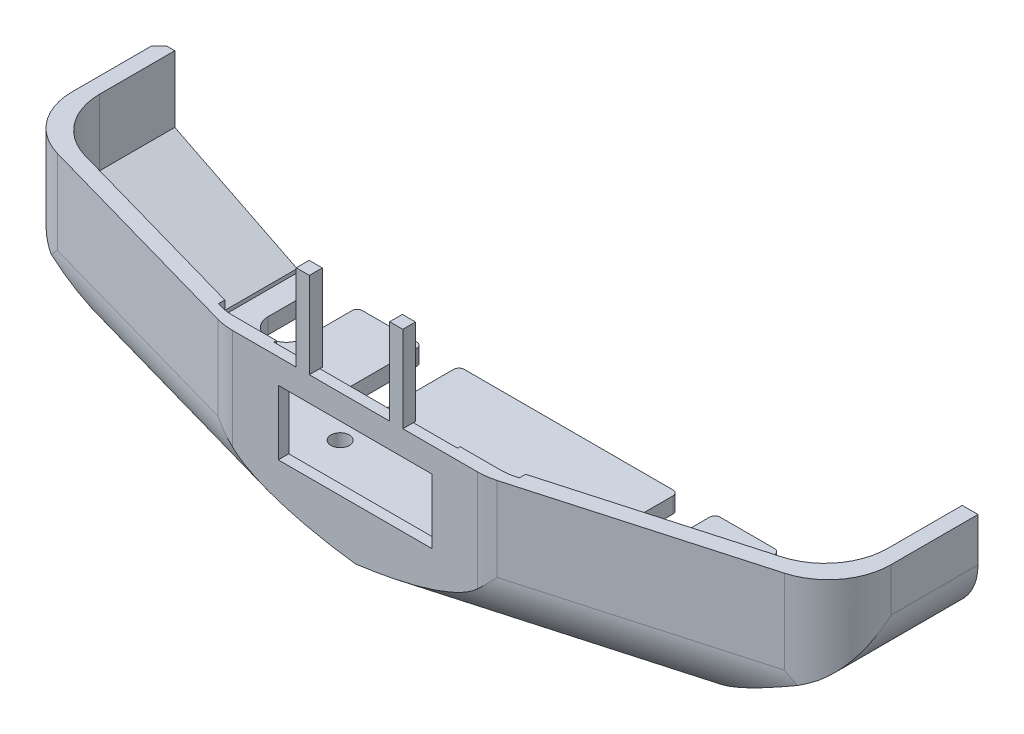
SolidWorks part; units mm, degrees
material "ABS"
ref_plane "Front Plane" through (0, 0, 0) normal (0, 0, 1) x (1, 0, 0)
ref_plane "Top Plane" through (0, 0, 0) normal (0, 1, 0) x (1, 0, 0)
ref_plane "Right Plane" through (0, 0, 0) normal (1, 0, 0) x (0, 0, -1)
sketch "Sketch1" plane through (0, 0, 0) normal (0, 0, 1) x (1, 0, 0)
  line L0 (-78, -21.6306) -> (78, -21.6306) construction
  line L1 (-51, -40.6306) -> (51, -40.6306)
  line L2 (-78, -27.1306) -> (-78, -12.6306)
  line L3 (-78, -12.6306) -> (78, -12.6306)
  line L4 (78, -27.1306) -> (78, -12.6306)
  line L8 (0, -21.6306) -> (0, 0) construction
  line L9 (78, -27.1306) -> (51, -40.6306)
  line L13 (-51, -40.6306) -> (-78, -27.1306)
  line L15 (0, -40.6306) -> (0, -21.6306) construction
  dimension "D1" = 9
  dimension "D2" = 156
  dimension "D3" = 13.5
  dimension "D5" = 102
  dimension "D6" = 19
extrude "Boss-Extrude1" add sketch "Sketch1" along normal blind 30 and the other way blind 10.64
sketch "Sketch2" plane through (0, -12.6306, 0) normal (0, 1, 0) x (1, 0, 0)
  line L0 (-78, -15) -> (-25, -30)
  line L1 (-78, -30) -> (-78, 10.64) construction
  line L2 (78, -30) -> (-78, -30) construction
  line L3 (-25, -30) -> (25, -30)
  line L4 (25, -30) -> (78, -15)
  line L5 (78, -30) -> (78, 10.64) construction
  line L6 (78, -15) -> (78, -44.6495)
  line L7 (78, -44.6495) -> (-78, -44.6495)
  line L8 (-78, -44.6495) -> (-78, -15)
  dimension "D1" = 50
  dimension "D2" = 15
extrude "Cut-Extrude1" cut sketch "Sketch2" against normal through all
shell "Shell1" thickness 3 removed face at (0, -26.7973, -10.64)
sketch "Sketch7" plane through (0, -15.6306, 0) normal (0, -1, 0) x (1, 0, 0)
  line L0 (-51, -10.64) -> (51, -10.64) construction
  line L3 (-24.5836, 27) -> (24.0964, 27)
  line L6 (75, -10.64) -> (-75, -10.64)
  line L7 (-78, -10.64) -> (-78, 15) construction
  line L8 (-25, 30) -> (25, 30) construction
  line L10 (75, -10.64) -> (75, 3.5182)
  line L13 (24.0964, 27) -> (66.2679, 15.0647)
  line L14 (-24.5836, 27) -> (-66.2679, 15.2026)
  line L15 (-75, -10.64) -> (-75, 3.6561)
  line L16 (78, -10.64) -> (78, 15) construction
  line L17 (-78, -10.64) -> (-78, 15) construction
  line L19 (-25, 30) -> (-78, 15) construction
  line L20 (78, 15) -> (25, 30) construction
  line L21 (63, 3.5182) -> (-66, 3.5182) construction
  arc A0 (75, 3.5182) -> (66.2679, 15.0647) centre (63, 3.5182) ccw
  arc A2 (-66.2679, 15.2026) -> (-75, 3.6561) centre (-63, 3.6561) ccw
  dimension "D8" = 3
  dimension "D1" = 3
  dimension "D2" = 3
  dimension "D3" = 3
  dimension "D4" = 12
  dimension "D5" = 12
  dimension "D6" = 48.68
extrude "Cut-Extrude4" cut sketch "Sketch7" against normal blind 10 and the other way blind 4
fillet "Fillet3" radius 8 2 edges at (-37.4377, -37.6306, 23.3621) (37.4377, -37.6306, 23.3621)
fillet "Fillet1" radius 12 6 edges at (78, -19.8806, 15) (25, -26.6306, 30) (38, -40.6306, 26.3208) (-78, -19.8806, 15) (-38, -40.6306, 26.3208) (-25, -26.6306, 30)
sketch "Sketch4" plane through (0, -37.6306, 0) normal (0, 1, 0) x (1, 0, 0)
  line L0 (-42.696, -12.86) -> (63.1659, -12.86) construction
  line L1 (0, 63.5417) -> (0, -42.2617) construction
  line L4 (-50.2918, 10.64) -> (50.2918, 10.64) construction
  circle A0 centre (-20, -12.86) radius 1.75
  circle A1 centre (20, -12.86) radius 1.75
  point P12 (0, 10.64)
  dimension "D1" = 3.5
  dimension "D2" = 3.5
  dimension "D3" = 20
  dimension "D4" = 20
  dimension "D5" = 23.5
extrude "Cut-Extrude2" cut sketch "Sketch4" against normal blind 30
sketch "Sketch10" plane through (0, -15.6306, 0) normal (0, 1, 0) x (1, 0, 0)
  line L0 (75, -3.5182) -> (75, -12.5933)
  line L1 (75, -12.5933) -> (66.2679, -15.0647)
  line L2 (53.2034, -18.7622) -> (67.5833, -14.6924) construction
  line L3 (66.2679, -15.0647) -> (24.0964, -27) construction
  line L4 (-0.2436, -27) -> (-0.2436, 8.92) construction
  line L5 (24.0964, -27) -> (-24.5836, -27) construction
  line L6 (-75.4873, -12.5933) -> (-69.5845, -13.6883)
  line L7 (-75, -3.6561) -> (-75.4873, -12.5933)
  line L8 (-75, -3.6561) -> (-75, 10.64) construction
  arc A0 (75, -3.5182) -> (66.2679, -15.0647) centre (63, -3.5182) cw
  arc A1 (-75, -3.6561) -> (-69.5845, -13.6883) centre (-63, -3.6561) ccw
  arc A2 (-75, -3.6561) -> (-66.2679, -15.2026) centre (-63, -3.6561) ccw construction
extrude "Boss-Extrude5" add sketch "Sketch10" against normal up to body separate body
sketch "Sketch11" plane through (0, -12.6306, 0) normal (0, 1, 0) x (1, 0, 0)
  line L0 (-24.5836, -27) -> (24.0964, -27)
  line L5 (24.3045, -27.5) -> (25.3045, -27.5)
  line L6 (-24.5836, -27) -> (-66.2679, -15.2026) construction
  line L7 (28.2864, -27) -> (28.2864, -25.8141)
  line L8 (28.2864, -25.8141) -> (24.0964, -27)
  line L10 (-29.1094, -25.7191) -> (-24.5836, -27)
  line L11 (-29.1094, -26.905) -> (-29.1094, -25.7191)
  line L12 (-24.34, -27.5) -> (-26.1441, -27.4957)
  line L16 (-24.34, -27.5) -> (24.3045, -27.5)
  line L17 (66.2679, -15.0647) -> (24.0964, -27) construction
  arc A0 (25.3045, -27.5) -> (28.2864, -27) centre (25.3045, -18.3581) ccw
  arc A1 (-26.1441, -27.4957) -> (-29.1094, -26.905) centre (-25.8652, -18.3581) cw
  dimension "D1" = 0.5
  dimension "D2" = 1
extrude "Cut-Extrude5" cut sketch "Sketch11" against normal blind 4
sketch "Sketch12" plane through (0, 0, 27) normal (0, 0, -1) x (-1, 0, 0)
  line L0 (24.5836, -37.6306) -> (-24.5836, -37.6306) construction
  line L1 (-14.65, -29.6306) -> (14.65, -29.6306)
  line L2 (-14.65, -29.6306) -> (-14.65, -17.3306)
  line L3 (-14.65, -17.3306) -> (14.65, -17.3306)
  line L4 (14.65, -29.6306) -> (14.65, -17.3306)
  line L5 (0, -37.6306) -> (0, -17.3306) construction
  dimension "D1" = 8
  dimension "D2" = 29.3
  dimension "D3" = 12.3
extrude "Cut-Extrude6" cut sketch "Sketch12" against normal up to surface (3 mm away) up to face at (0, -25.9749, 30)
sketch "Sketch13" plane through (0, -12.6306, 0) normal (0, 1, 0) x (1, 0, 0)
  line L5 (23.3346, -30) -> (-23.3346, -30) construction
  line L11 (0, -28) -> (17.5, -28)
  line L12 (17.5, -28) -> (17.5, -24)
  line L13 (17.5, -24) -> (-17.5, -24)
  line L14 (-17.5, -24) -> (-17.5, -28)
  line L15 (-17.5, -28) -> (0, -28)
  dimension "D1" = 35
  dimension "D2" = 4
  dimension "D3" = 2
extrude "Cut-Extrude7" cut sketch "Sketch13" against normal blind 22
fillet "Fillet2" radius 10 4 edges at (-78, -27.1306, -2.3576) (-51, -40.6306, -0.2349) (51, -40.6306, -0.2349) (78, -27.1306, -2.3576) tangent propagation no
sketch "Sketch14" plane through (0, 0, 30) normal (0, 0, 1) x (1, 0, 0)
  line L0 (0, -12.6306) -> (0, -39.4493) construction
  line L1 (23.3346, -12.6306) -> (-23.3346, -12.6306) construction
  line L2 (-11.23, -12.6306) -> (-11.23, 3.7694)
  line L3 (-11.23, 3.7694) -> (-8.73, 3.7694)
  line L4 (-8.73, 3.7694) -> (-8.73, -12.6306)
  line L5 (-11.23, -12.6306) -> (-8.73, -12.6306)
  line L6 (6.57, -12.6306) -> (6.57, 3.7694)
  line L7 (6.57, 3.7694) -> (9.07, 3.7694)
  line L8 (9.07, 3.7694) -> (9.07, -12.6306)
  line L9 (9.07, -12.6306) -> (6.57, -12.6306)
  line L10 (-25.73, -16.6306) -> (-25.73, -34.2902) construction
  line L11 (-23.3346, -16.6306) -> (-26.6025, -16.6306) construction
  dimension "D1" = 2.5
  dimension "D2" = 2.5
  dimension "D3" = 15.3
  dimension "D4" = 25.73
  dimension "D5" = 14.5
  dimension "D6" = 16.4
extrude "Boss-Extrude4" add sketch "Sketch14" against normal up to surface (2.4691 mm away) up to face at (-25.2421, -14.6306, 27.4979)
sketch "Sketch15" plane through (8.8979, 0, 31.4394) normal (-0.2723, 0, -0.9622) x (-0.9622, 0, 0.2723)
  line L1 (-59.6609, -12.6306) -> (-20.1876, -12.6306) construction
  circle A0 centre (-33.8593, -23.6306) radius 7.6
  dimension "D1" = 15.2
  dimension "D2" = 11
extrude "Cut-Extrude8" [suppressed] cut sketch "Sketch15" against normal offset from surface 1.5 and the other way blind 10 up to face at (47.9352, -20.6306, 23.5089)
sketch "Sketch16" [suppressed] plane through (9.4463, 0, 32.9046) normal (-0.2759, 0, -0.9612) x (-0.9612, 0, 0.2759)
  line L0 (-33.8593, -16.0306) -> (-33.8593, -31.2306) construction
  circle A0 centre (-33.8593, -23.6306) radius 7.6 construction
  circle A1 centre (-33.8593, -23.6306) radius 7.6 construction
  circle A2 centre (-33.8593, -23.6306) radius 1.212
  circle A3 centre (-33.8593, -19.6306) radius 1.25
  circle A4 centre (-30.6079, -21.5078) radius 1.25
  circle A5 centre (-30.6079, -25.2622) radius 1.25
  circle A6 centre (-33.8593, -27.1394) radius 1.25
  circle A7 centre (-37.1106, -25.2622) radius 1.25
  circle A11 centre (-37.1106, -21.5078) radius 1.25
  point P21 (-33.8593, -23.385)
  dimension "D3" = 2.5
  dimension "D1" = 4
  dimension "D2" = 6
extrude "Cut-Extrude9" [suppressed] cut sketch "Sketch16" against normal blind 1.5
sketch "Sketch17" plane through (-8.8979, 0, 31.4394) normal (0.2723, 0, -0.9622) x (-0.9622, 0, -0.2723)
  line L0 (25.2116, -21.1417) -> (50.6116, -21.1417) construction
  line L1 (28.4116, -15.1417) -> (47.4116, -15.1417)
  line L2 (28.4116, -15.1417) -> (28.4116, -27.1417)
  line L3 (28.4116, -27.1417) -> (47.4116, -27.1417)
  line L4 (47.4116, -15.1417) -> (47.4116, -27.1417)
  circle A0 centre (25.2116, -21.1417) radius 1.75
  circle A1 centre (50.6116, -21.1417) radius 1.75
  point P6 (37.9116, -21.1417)
  point P7 (37.9116, -15.1417)
  point P8 (47.4116, -21.1417)
  dimension "D4" = 3.5
  dimension "D1" = 19
  dimension "D2" = 12
  dimension "D3" = 25.4
extrude "Cut-Extrude10" [suppressed] cut sketch "Sketch17" against normal blind 10
sketch "Sketch18" plane through (0, -40.6306, 0) normal (0, -1, 0) x (1, 0, 0)
  line L0 (0, 0) -> (0, -10.64) construction
  line L1 (-48.6393, -10.64) -> (48.6393, -10.64) construction
  line L2 (-43.75, -0.64) -> (43.75, -0.64) construction
  line L3 (-24.38, 3.86) -> (24.38, 3.86) construction
  line L4 (-27.88, 3.86) -> (-27.88, -10.64)
  line L5 (-47.25, -0.64) -> (-47.25, -10.64)
  line L6 (-40.25, -0.64) -> (-40.25, -10.64)
  line L7 (-40.25, -10.64) -> (-47.25, -10.64)
  line L8 (-20.88, 3.86) -> (-20.88, -10.64)
  line L9 (-20.88, -10.64) -> (-27.88, -10.64)
  line L10 (20.88, 3.86) -> (20.88, -10.64)
  line L11 (20.88, -10.64) -> (27.88, -10.64)
  line L12 (27.88, -10.64) -> (27.88, 3.86)
  line L13 (40.25, -0.64) -> (40.25, -10.64)
  line L14 (40.25, -10.64) -> (47.25, -10.64)
  line L15 (47.25, -10.64) -> (47.25, -0.64)
  circle A0 centre (-43.75, -0.64) radius 3.5
  circle A1 centre (43.75, -0.64) radius 3.5
  circle A2 centre (24.38, 3.86) radius 3.5
  circle A3 centre (-24.38, 3.86) radius 3.5
  point P8 (0, -0.64)
  point P12 (0, 3.86)
  line M6 (-48.6393, -10.64) -> (48.6393, -10.64)
  dimension "D3" = 7
  dimension "D1" = 87.5
  dimension "D2" = 10
  dimension "D4" = 19.37
  dimension "D5" = 4.5
extrude "Cut-Extrude11" cut sketch "Sketch18" against normal blind 10 contours A3 L4 L8 M6 | A3 | A0 | A0 L5 L6 M6 | A2 L10 L12 M6 | A2 | A1 L13 L15 M6 | A1 region at (-24.38, -40.6306, -4.7385) region at (43.75, -40.6306, -6.9724) region at (24.38, -40.6306, -4.7385) region at (-43.75, -40.6306, -6.9724) region at (-24.38, -40.6306, 3.86) region at (-43.75, -40.6306, -0.64) region at (24.38, -40.6306, 3.86) region at (43.75, -40.6306, -0.64)
sketch "Sketch19" plane through (0, -37.6306, 0) normal (0, 1, 0) x (1, 0, 0)
  line L0 (51.6996, -7.3977) -> (51.6996, 10.64)
  line L1 (51.6996, 10.64) -> (-51.6996, 10.64)
  line L2 (-51.6996, 10.64) -> (-51.6996, -7.3977)
  line L3 (-51.6996, -7.3977) -> (-32.5, -21.8972)
  line L4 (-32.5, -21.8972) -> (32.5, -21.8972)
  line L5 (32.5, -21.8972) -> (51.6996, -7.3977)
  point P12 (0, -21.8972)
  point P14 (0, 10.64)
  dimension "D1" = 65
extrude "Cut-Extrude12" cut sketch "Sketch19" along normal blind 10
sketch "Sketch20" plane through (0, -12.6306, 0) normal (0, 1, 0) x (1, 0, 0)
  line L1 (-75, 10.64) -> (-76.5, 10.64)
  line L2 (-75, 10.64) -> (-75, -3.36)
  line L3 (-75, -3.36) -> (-76.5, -3.36)
  line L4 (-76.5, 10.64) -> (-76.5, -3.36)
  line L5 (75, 10.64) -> (76.5, 10.64)
  line L6 (75, 10.64) -> (75, -3.36)
  line L7 (75, -3.36) -> (76.5, -3.36)
  line L8 (76.5, 10.64) -> (76.5, -3.36)
  dimension "D1" = 1.5
  dimension "D2" = 14
extrude "Boss-Extrude6" [suppressed] add sketch "Sketch20" along normal blind 11
sketch "Sketch21" [suppressed] plane through (-75.75, 0, 0) normal (-1, 0, 0) x (0, 0, 1)
  line L0 (-10.64, -1.6306) -> (-10.64, -12.6306) construction
  line L1 (-10.64, -12.6306) -> (3.36, -12.6306) construction
  circle A0 centre (-1.64, -7.1306) radius 1.75
  dimension "D3" = 3.5
  dimension "D1" = 9
  dimension "D2" = 5.5
extrude "Cut-Extrude13" [suppressed] cut sketch "Sketch21" against normal through all
fillet "Fillet4" [suppressed] radius 2
chamfer "Chamfer1" distance 1.5 angle 45 4 edges at (-78, -16.7905, -10.64) (-76.5065, -26.2076, -10.64) (-62.7918, -34.7347, -10.64) (-50.9368, -40.3631, -10.64)
fillet "Fillet5" radius 1 8 edges at (-27.88, -39.1306, -10.64) (-20.88, -39.1306, -10.64) (-40.25, -39.1306, -10.64) (-47.25, -38.3806, -10.64) (20.88, -39.1306, -10.64) (27.88, -39.1306, -10.64) (40.25, -39.1306, -10.64) (47.25, -39.1306, -10.64)
